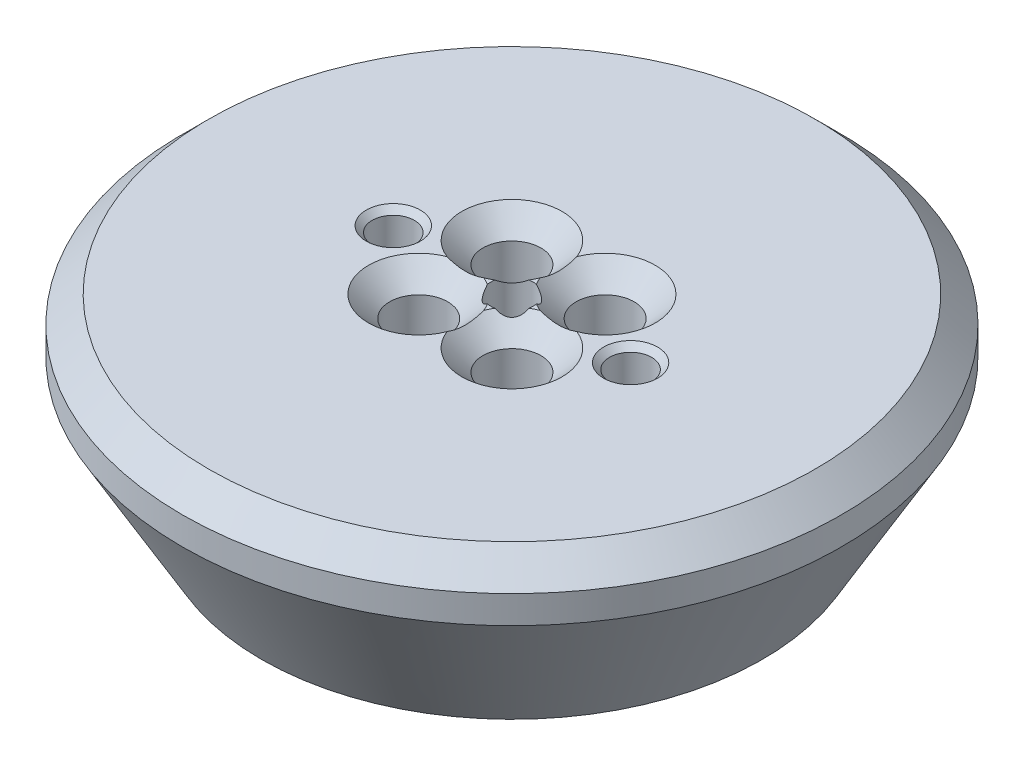
SolidWorks part; units mm, degrees
ref_plane "Front Plane" through (0, 0, 0) normal (0, 0, 1) x (1, 0, 0)
ref_plane "Top Plane" through (0, 0, 0) normal (0, 1, 0) x (1, 0, 0)
ref_plane "Right Plane" through (0, 0, 0) normal (1, 0, 0) x (0, 0, -1)
sketch "Sketch1" plane through (0, 0, 0) normal (0, 1, 0) x (1, 0, 0)
  circle A0 centre (0, 0) radius 12.5
  dimension "D1" = 25
extrude "Boss-Extrude1" add sketch "Sketch1" along normal blind 3
sketch "Sketch2" plane through (0, 3, 0) normal (0, 1, 0) x (1, 0, 0)
  circle A0 centre (0, 0) radius 0.8
  dimension "D1" = 1.6
extrude "Cut-Extrude1" cut sketch "Sketch2" against normal through all both and the other way through all
hole_wizard "CSK for M2 Flat Head Machine Screw1" positions "Sketch3" profile "Sketch4" countersink size "M2" standard "ANSI Metric"
sketch "Sketch3" plane through (0, 3, 0) normal (0, 1, 0) x (1, 0, 0)
  line L1 (-1.7678, 1.7678) -> (1.7678, 1.7678)
  line L2 (-1.7678, 1.7678) -> (-1.7678, -1.7678)
  line L3 (-1.7678, -1.7678) -> (1.7678, -1.7678)
  line L4 (1.7678, 1.7678) -> (1.7678, -1.7678)
  line L5 (-1.7678, 1.7678) -> (1.7678, -1.7678) construction
  point P0 (-1.7678, 1.7678)
  point P2 (1.7678, 1.7678)
  point P4 (1.7678, -1.7678)
  point P6 (-1.7678, -1.7678)
  point P120 (0, 0)
  dimension "D1" = 5
sketch "Sketch4" plane through (-1.7678, 3, -1.7678) normal (1, 0, 0) x (0, 0, 1)
  line L0 (0, 0) -> (0, 5.6609)
  line L1 (0, 5.6609) -> (1.1, 5)
  line L2 (1.1, 5) -> (1.1, 0.8)
  line L3 (1.1, 0.8) -> (1.9, 0)
  line L5 (1.9, 0) -> (0, 0)
  line L6 (-1.1, 0.8) -> (-1.9, 0) construction
  line L10 (0, 5.6609) -> (-1.1, 5) construction
  line L11 (0, -6.35) -> (0, 107.95) construction
  dimension "Hole Dia." = 2.2
  dimension "Hole Depth" = 5
  dimension "Near C'Sink Dia." = 3.8
  dimension "Near C'Sink Angle" = 90
  dimension "Drill Angle" = 118
sketch "Sketch6" plane through (0, 0, 0) normal (0, 0, 1) x (1, 0, 0)
  line L0 (-12.5, 0) -> (-12.5, -1.25)
  line L1 (-12.5, -1.25) -> (-7.2, -1.25)
  line L2 (-7.2, -1.25) -> (-5, 0)
  line L3 (-5, 0) -> (-12.5, 0)
  line L4 (0, 0) -> (0, -5.6432) construction
  dimension "D1" = 1.25
  dimension "D2" = 5
  dimension "D3" = 7.2
revolve "Revolve1" add sketch "Sketch6" angle 360 about L4
sketch "Sketch7" plane through (0, -1.25, 0) normal (0, -1, 0) x (1, 0, 0)
  circle A0 centre (0, 0) radius 7.2 construction
  circle A1 centre (0, 0) radius 12.5
  circle A2 centre (0, 0) radius 12.5
  circle A3 centre (0, 0) radius 7.2
  dimension "D1" = 0
extrude "Boss-Extrude2" add sketch "Sketch7" along normal blind 3
sketch "Sketch11" plane through (0, 3, 0) normal (0, 1, 0) x (1, 0, 0)
  line L0 (0, 0) -> (-3.2481, 0) construction
  line L1 (-7.25, 5.1678) -> (-7.25, -5.1678)
  line L2 (-7.25, -5.1678) -> (7.25, -5.1678)
  line L3 (7.25, -5.1678) -> (7.25, 5.1678)
  line L4 (7.25, 5.1678) -> (-7.25, 5.1678)
  line L5 (-7.25, 5.1678) -> (7.25, -5.1678) construction
  line L6 (-1.7678, -3.6678) -> (-1.7678, -5.1678) construction
  line L7 (-0.6889, -3.6678) -> (-2.8466, -3.6678) construction
  circle A0 centre (0, 0) radius 10
  arc A4 (-2.4642, 0) -> (0, -2.4642) centre (-1.7678, -1.7678) ccw construction
  dimension "D1" = 1.5
  dimension "D3" = 20
  dimension "D2" = 14.5
extrude "Boss-Extrude3" [suppressed] add sketch "Sketch11" along normal blind 3
fillet "Fillet2" [suppressed] radius 5
fillet "Fillet3" [suppressed] radius 1
fillet "Fillet1" radius 1 2 edges at (0, 0, 5) (0, -1.25, 7.2)
loft "Loft2" [suppressed] add
sketch "Sketch14" [suppressed] plane through (0, 4.5, 0) normal (0, 1, 0) x (1, 0, 0)
  circle A0 centre (0, 0) radius 10 construction
  circle A1 centre (0, 0) radius 10
extrude "Cut-Extrude2" [suppressed] cut sketch "Sketch14" against normal through all both and the other way through all
combine bodies "Combine1" [suppressed] operation type add bodies to combine 110 107
chamfer "Chamfer1" distance 1 angle 45 1 edges at (0, 3, 12.5)
chamfer "Chamfer2" distance 1 angle 45 1 edges at (0, -4.25, -7.2)
chamfer "Chamfer3" distance 3 angle 60 1 edges at (0, -4.25, -12.5) first distance on face at (0, -4.25, -8.2)
hole_wizard "M2x0.4 Tapped Hole1" positions "Sketch8" profile "Sketch9" tap size "M2x0.4" standard "ANSI Metric"
sketch "Sketch8" plane through (0, 3, 0) normal (0, 1, 0) x (1, 0, 0)
  line L0 (-4.5, 0) -> (4.5, 0) construction
  point P0 (-4.5, 0)
  point P2 (4.5, 0)
  dimension "D1" = 9
sketch "Sketch9" plane through (-4.5, 3, 0) normal (1, 0, 0) x (0, 0, 1)
  line L0 (0, 0) -> (0, 5.6807)
  line L1 (0, 5.6807) -> (0.8, 5.2)
  line L2 (0.8, 5.2) -> (0.8, 0.225)
  line L3 (0.8, 0.225) -> (1.025, 0)
  line L5 (1.025, 0) -> (0, 0)
  line L6 (-0.8, 0.225) -> (-1.025, 0) construction
  line L10 (0, 5.6807) -> (-0.8, 5.2) construction
  line L11 (0, -6.35) -> (0, 107.95) construction
  dimension "Tap Drill Dia." = 1.6
  dimension "Tap Drill Depth" = 5.2
  dimension "Near C'Sink Dia." = 2.05
  dimension "Near C'Sink Angle" = 90
  dimension "Drill Angle" = 118
cosmetic thread "Hole Thread1" parameters "D1"=2.4801, "D2"=2
cosmetic thread "Hole Thread2" parameters "D1"=2.4801, "D2"=2
